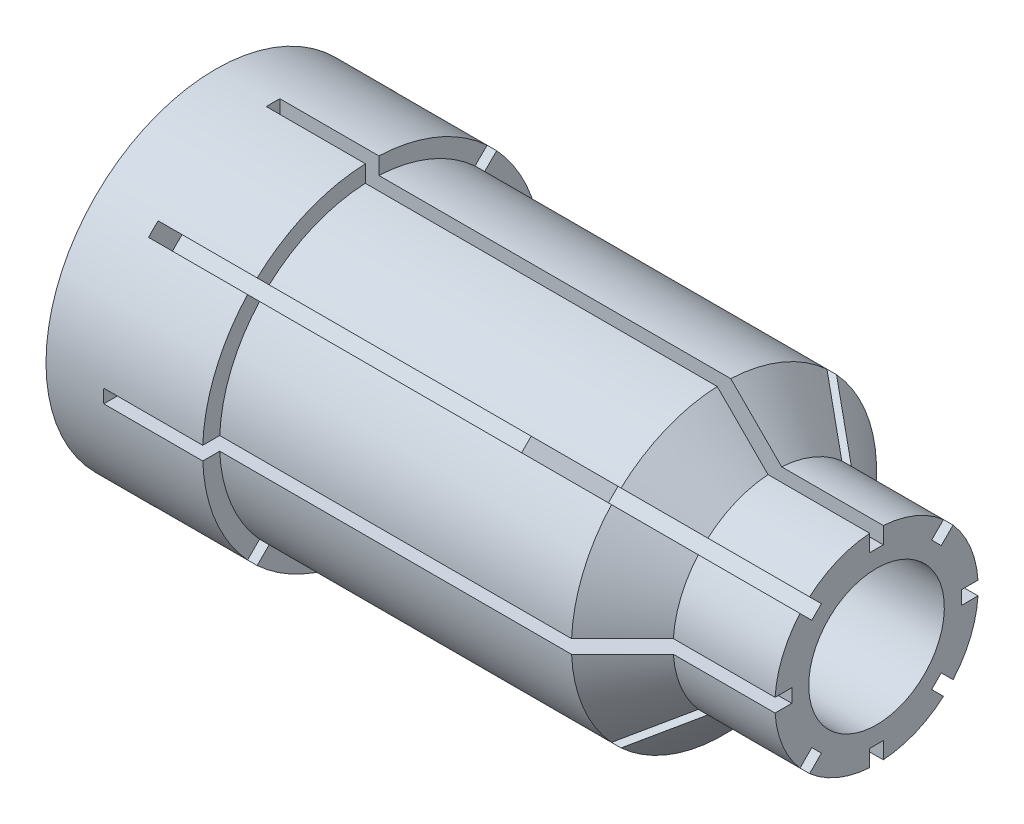
SolidWorks part; units mm, degrees
ref_plane "Ön Düzlem" through (0, 0, 0) normal (0, 0, 1) x (1, 0, 0)
ref_plane "Üst Düzlem" through (0, 0, 0) normal (0, 1, 0) x (1, 0, 0)
ref_plane "Sağ Düzlem" through (0, 0, 0) normal (1, 0, 0) x (0, 0, -1)
sketch "Sketch1" plane through (0, 0, 0) normal (0, 0, 1) x (1, 0, 0)
  line L5 (-10, 3) -> (-10, 2)
  line L6 (-10, 2) -> (-16, 2)
  line L7 (-16, 2) -> (-17.5, 3.5)
  line L8 (-17.5, 3.5) -> (-29.5, 3.5)
  line L9 (-29.5, 3.5) -> (-29.5, 5)
  line L10 (-29.5, 5) -> (-24.88, 5)
  line L13 (-24.88, 5) -> (-24.88, 4.5)
  line L14 (-24.88, 4.5) -> (-14.5, 4.5)
  line L15 (-14.5, 4.5) -> (-13, 3)
  line L16 (-13, 3) -> (-10, 3)
  line L17 (0, 0) -> (-10, 0) construction
  dimension "D2" = 10
  dimension "D3" = 2
  dimension "D4" = 10
  dimension "D7" = 1.5
  dimension "D8" = 6
  dimension "D9" = 12
  dimension "D11" = 1.5
  dimension "D12" = 4.62
  dimension "D13" = 0.5
  dimension "D14" = 135
  dimension "D15" = 15
  dimension "D16" = 3
  dimension "D17" = 1.5
revolve "Revolve1" add sketch "Sketch1" angle 360 about L17
sketch "Sketch3" plane through (0, 0, 0) normal (0, 0, 1) x (1, 0, 0)
  line L0 (-29.5, 5) -> (-29.5, -5) construction
  line L5 (-14.5, 4.5) -> (-13, 3)
  line L6 (-24.8846, 4.5) -> (-14.5, 4.5)
  line L7 (-16, 2.5) -> (-17.5, 4)
  line L9 (-13, 3) -> (-10, 3)
  line L11 (-16, 2.5) -> (-10, 2.5)
  line L12 (-10, 3) -> (-10, 2.5)
  line L14 (-27.8, 4) -> (-27.8, 5.5)
  line L15 (-27.8, 5.5) -> (-24.8846, 5.5)
  line L16 (-24.8846, 4.5) -> (-24.8846, 5.5)
  line L17 (-27.8, 4) -> (-17.5, 4)
  dimension "D2" = 1.5
  dimension "D3" = 0.5
  dimension "D4" = 3
  dimension "D5" = 1.5
  dimension "D6" = 10.3
  dimension "D7" = 6
  dimension "D8" = 1
  dimension "D9" = 1.7
  dimension "D10" = 2.9154
  dimension "D11" = 3
  dimension "D12" = 2
  dimension "D13" = 4
  dimension "D14" = 135
extrude "Cut-Extrude2" cut sketch "Sketch3" against normal blind 0.2 and the other way blind 0.2
pattern_circular "CirPattern2" count 8 over 360 about axis through (-10, 0, 0) along (1, 0, 0) of "Cut-Extrude2"
sketch "Sketch4" plane through (-24.88, 0, 0) normal (1, 0, 0) x (0, 0, -1)
  line L0 (-0.2, 4.996) -> (-0.2, 4) construction
  line L1 (-0.2, 4.498) -> (0.2, 4.498)
  line L2 (-0.2, 4.498) -> (-0.2, 5.248)
  line L3 (-0.2, 5.248) -> (0.2, 5.248)
  line L4 (0.2, 4.498) -> (0.2, 5.248)
  line L5 (0.2, 4.4956) -> (0.2, 2.9933) construction
  dimension "D1" = 0.75
extrude "Cut-Extrude3" cut sketch "Sketch4" against normal blind 1
pattern_circular "CirPattern3" count 8 over 360 about axis through (-24.88, 0, 0) along (1, 0, 0) of "Cut-Extrude3"
